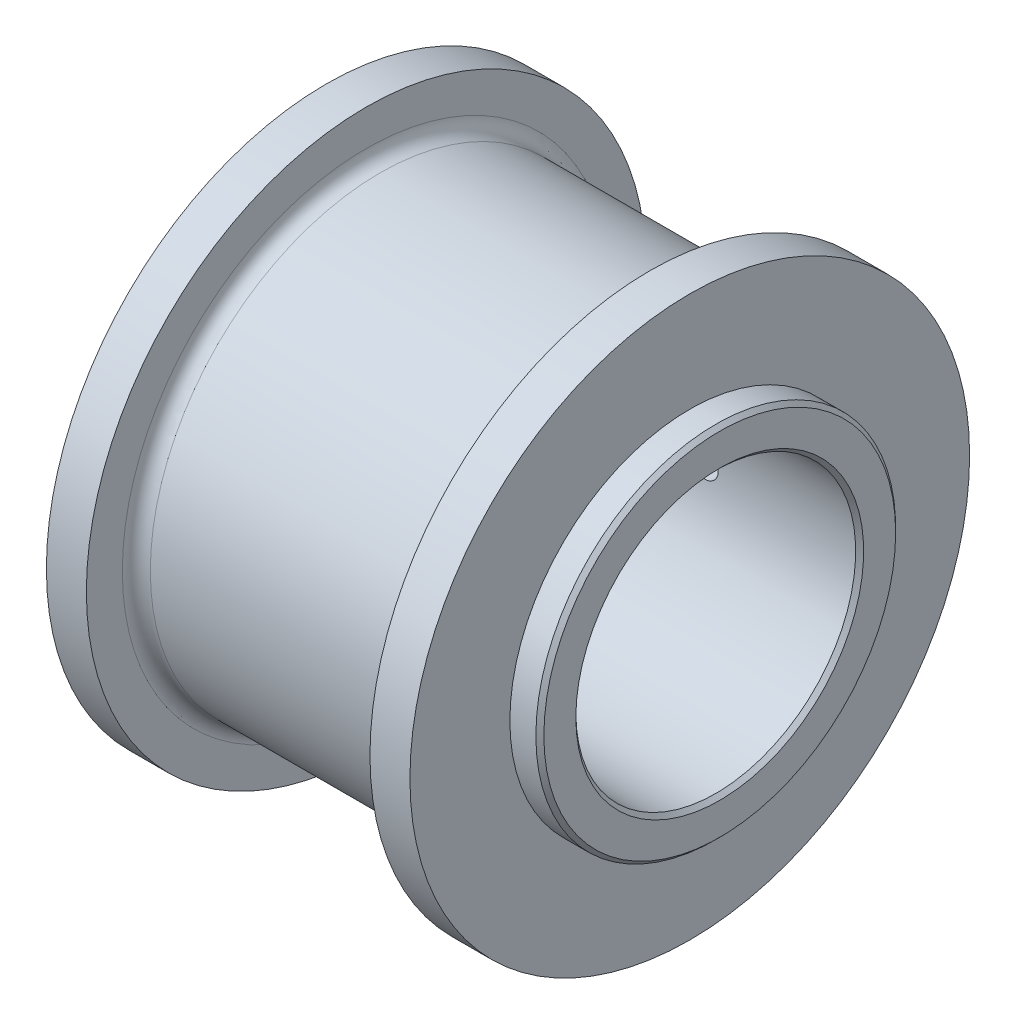
SolidWorks part; units mm, degrees
ref_plane "Front Plane" through (0, 0, 0) normal (0, 0, 1) x (1, 0, 0)
ref_plane "Top Plane" through (0, 0, 0) normal (0, 1, 0) x (1, 0, 0)
ref_plane "Right Plane" through (0, 0, 0) normal (1, 0, 0) x (0, 0, -1)
sketch "Sketch1" plane through (0, 0, 0) normal (0, 0, 1) x (1, 0, 0)
  line L0 (3.81, 35.56) -> (8.89, 35.56)
  line L1 (8.89, 35.56) -> (8.89, 29.21)
  line L3 (44.925, 29.21) -> (44.925, 35.56)
  line L4 (44.925, 35.56) -> (50.005, 35.56)
  line L5 (50.005, 35.56) -> (50.005, 22.86)
  line L6 (50.005, 22.86) -> (53.815, 22.86)
  line L7 (53.815, 22.86) -> (53.815, 17.78)
  line L8 (53.815, 17.78) -> (15.08, 17.78)
  line L9 (15.08, 17.78) -> (15.08, 16.002)
  line L10 (15.08, 16.002) -> (5.08, 16.002)
  line L11 (5.08, 16.002) -> (5.08, 11.08)
  line L12 (5.08, 11.08) -> (0, 11.08)
  line L13 (0, 11.08) -> (0, 22.86)
  line L14 (0, 22.86) -> (3.81, 22.86)
  line L15 (3.81, 22.86) -> (3.81, 35.56)
  line L16 (0, 0) -> (18.9296, 0) construction
  line L18 (8.89, 29.21) -> (44.925, 29.21)
  point P2 (8.89, 29.21)
  point P19 (9.4648, 0)
  point P20 (0, 0)
  point P21 (44.925, 29.21)
  point P22 (44.3361, 29.21)
  dimension "D2" = 10
  dimension "D3" = 38.735
  dimension "D1" = 16.002
  dimension "D5" = 17.78
  dimension "D6" = 22.86
  dimension "D7" = 22.86
  dimension "D8" = 5.08
  dimension "D9" = 35.56
  dimension "D10" = 35.56
  dimension "D14" = 3.81
  dimension "D15" = 3.81
  dimension "D16" = 5.08
  dimension "D11" = 29.21
  dimension "D12" = 11.08
revolve "Revolve1" add sketch "Sketch1" angle 360 about L16
ref_plane "Plane1" through (34.257, 0, 0) normal (1, 0, 0) x (0, 0, -1)
sketch "Sketch2" plane through (34.257, 0, 0) normal (1, 0, 0) x (0, 0, -1)
  point P0 (0, 0)
ref_plane "Plane2" through (0, 0, -29.21) normal (0, 0, -1) x (-1, 0, 0)
sketch "Sketch3" plane through (0, 0, -29.21) normal (0, 0, -1) x (-1, 0, 0)
  line L0 (0, 0) -> (-31.082, 0) construction
  line L1 (-37.432, 25.4) -> (-31.082, 25.4)
  line L2 (-37.432, 25.4) -> (-37.432, -25.4)
  line L3 (-37.432, -25.4) -> (-31.082, -25.4)
  line L4 (-31.082, 25.4) -> (-31.082, -25.4)
  line L5 (-34.257, 0) -> (-34.257, 25.4) construction
  point P4 (0, 0)
  point P8 (-34.257, 0)
  dimension "D1" = 50.8
  dimension "D2" = 6.35
extrude "Cut-Extrude1" cut sketch "Sketch3" against normal blind 2.54
sketch "Sketch4" plane through (0, 0, -29.21) normal (0, 0, -1) x (-1, 0, 0)
  point P0 (-34.257, 0)
hole_wizard "1/8 (0.125) Diameter Hole1" positions "Sketch4" profile "Sketch5" hole size "1/8" standard "ANSI Inch" end condition up to next
sketch "Sketch5" plane through (34.257, 0, -29.21) normal (1, 0, 0) x (0, 1, 0)
  line L0 (0, 0) -> (0, 11.43)
  line L1 (0, 11.43) -> (1.5875, 11.43)
  line L2 (1.5875, 11.43) -> (1.5875, 0)
  line L5 (1.5875, 0) -> (0, 0)
  line L11 (0, -6.35) -> (0, 107.95) construction
  dimension "Thru Hole Dia." = 3.175
  dimension "Thru Hole Depth" = 11.43
fillet "Fillet2" radius 1.778 2 edges at (8.89, 0, 29.21) (44.925, 0, 29.21)
chamfer "Chamfer1" distance 0.508 4 edges at (0, 0, 22.86) (53.815, 0, 22.86) (53.815, 0, 17.78) (0, 0, 11.08)
equation "\"bearing_radius\"= 0.629921"
equation "\"bearing_width\"=0.393701"
equation "\"D2@Sketch1\"=\"bearing_width\""
equation "\"kero_radius\"=0.334in"
equation "\"lox_radius\"=0.23622in"
equation "\"Cavity_width\"=0.031in"
equation "\"tooth_width\"=0.01in"
equation "\"cavity_depth\"=0.031in"
equation "\"seal_step\"=0.01in"
equation "\"purge_length\"=0.04in"
equation "\"insert_radius\" = 0.7in"
equation "\"recycle_groove width\" = 0.06in"
equation "\"recycle_groove_depth\" = 0.06in"
equation "\"N2_purge_width\"= .06in"
equation "\"N2_purge_depth\"= .06in"
equation "\"drain_width\"= .06in"
equation "\"drain_depth\"= .06in"
equation "\"radial_clearance\"= .002in"
equation "\"IPS_flange_width\"= .2in"
equation "\"IPS_flange_radius\" = 1.4in"
equation "\"IPS_LOX_male_radius\"= .9in"
equation "\"IPS_Kero_male_radius\" = .9in"
equation "\"IPS_radius\"= 1.15in"
equation "\"D5@Sketch1\"=\"insert_radius\""
equation "\"InsertLength\"= 1.525in"
equation "\"D3@Sketch1\"=\"InsertLength\""
equation "\"D6@Sketch1\"=\"IPS_Kero_male_radius\""
equation "\"D7@Sketch1\"=\"IPS_LOX_male_radius\""
equation "\"D8@Sketch1\"=\"IPS_flange_width\""
equation "\"D9@Sketch1\"=\"IPS_flange_radius\""
equation "\"D10@Sketch1\"=\"IPS_flange_radius\""
equation "\"D12@Sketch1\"=\"lox_radius\"+.2"
